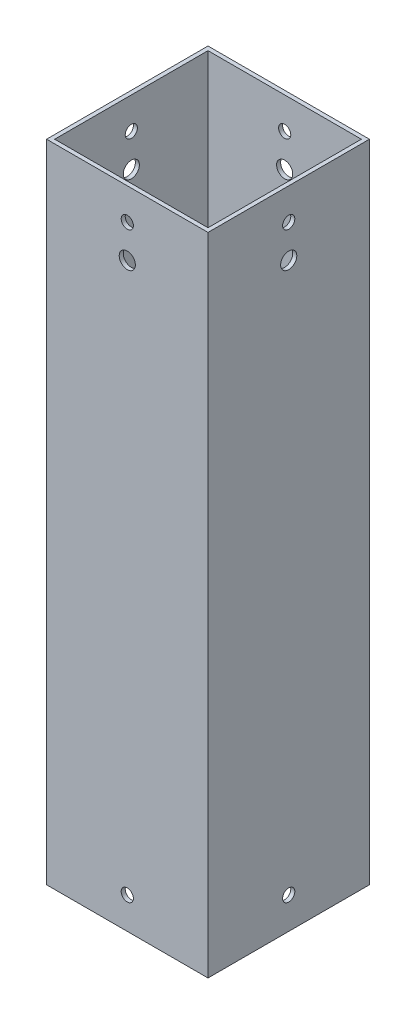
SolidWorks part; units mm, degrees
material "6061 Alloy"
ref_plane "Front Plane" through (0, 0, 0) normal (0, 0, 1) x (1, 0, 0)
ref_plane "Top Plane" through (0, 0, 0) normal (0, 1, 0) x (1, 0, 0)
ref_plane "Right Plane" through (0, 0, 0) normal (1, 0, 0) x (0, 0, -1)
sketch "Sketch1" plane through (0, 0, 0) normal (0, 1, 0) x (1, 0, 0)
  line L1 (-30.1625, 30.1625) -> (30.1625, 30.1625)
  line L2 (-30.1625, 30.1625) -> (-30.1625, -30.1625)
  line L3 (-30.1625, -30.1625) -> (30.1625, -30.1625)
  line L4 (30.1625, 30.1625) -> (30.1625, -30.1625)
  line L5 (-31.75, 31.75) -> (31.75, 31.75)
  line L6 (-31.75, 31.75) -> (-31.75, -31.75)
  line L7 (-31.75, -31.75) -> (31.75, -31.75)
  line L8 (31.75, 31.75) -> (31.75, -31.75)
  point P2 (-31.75, 0)
  point P11 (-30.1625, 0)
  point P12 (0, 30.1625)
  point P13 (0, 31.75)
  dimension "D1" = 60.325
  dimension "1.95" = 60.325
  dimension "2.05" = 63.5
  dimension "D2" = 63.5
extrude "Boss-Extrude1" add sketch "Sketch1" along normal blind 254
ref_plane "Plane1" through (0, 152.4, 0) normal (0, 1, 0) x (1, 0, 0)
sketch "Sketch3" plane through (0, 152.4, 0) normal (0, 1, 0) x (1, 0, 0)
  line L1 (-30.1625, 30.1625) -> (30.1625, 30.1625)
  line L2 (-30.1625, 30.1625) -> (-30.1625, -30.1625)
  line L3 (-30.1625, -30.1625) -> (30.1625, -30.1625)
  line L4 (30.1625, 30.1625) -> (30.1625, -30.1625)
extrude "Boss-Extrude3" add sketch "Sketch3" against normal blind 2.54
sketch "Sketch4" plane through (-30.1625, 0, 0) normal (1, 0, 0) x (0, 0, -1)
  line L0 (-31.75, 254) -> (31.75, 254) construction
  line L1 (31.75, 254) -> (31.75, 0) construction
  circle A0 centre (0, 241.5876) radius 2.4
  dimension "D1" = 4.8
  dimension "D2" = 12.4124
  dimension "D3" = 31.75
extrude "Cut-Extrude1" cut sketch "Sketch4" along normal through all both and the other way through all
sketch "Sketch5" plane through (0, 0, -31.75) normal (0, 0, -1) x (-1, 0, 0)
  line L0 (-31.75, 254) -> (31.75, 254) construction
  line L1 (31.75, 254) -> (31.75, 0) construction
  circle A0 centre (0, 241.5876) radius 2.4
  dimension "D1" = 4.8
  dimension "D2" = 12.4124
  dimension "D3" = 31.75
extrude "Cut-Extrude2" cut sketch "Sketch5" against normal through all
sketch "Sketch6" plane through (31.75, 0, 0) normal (1, 0, 0) x (0, 0, -1)
  line L0 (-31.75, 0) -> (31.75, 0) construction
  line L1 (31.75, 254) -> (31.75, 0) construction
  circle A0 centre (0, 12.4124) radius 2.4
  dimension "D1" = 12.4124
  dimension "D2" = 4.8
  dimension "D3" = 31.75
extrude "Cut-Extrude3" cut sketch "Sketch6" against normal through all both and the other way through all
sketch "Sketch7" plane through (0, 0, -31.75) normal (0, 0, -1) x (-1, 0, 0)
  line L0 (-31.75, 0) -> (31.75, 0) construction
  circle A0 centre (0, 12.4124) radius 2.4
  dimension "D1" = 4.8
  dimension "D2" = 12.4124
  dimension "D3" = 31.75
extrude "Cut-Extrude4" cut sketch "Sketch7" against normal through all both
sketch "Sketch8" plane through (0, 0, -31.75) normal (0, 0, -1) x (-1, 0, 0)
  line L0 (-31.75, 254) -> (31.75, 254) construction
  line L1 (-31.75, 254) -> (-31.75, 0) construction
  circle A0 centre (0, 228.6) radius 3.175
  dimension "D1" = 6.35
  dimension "D2" = 25.4
  dimension "D3" = 31.75
extrude "Cut-Extrude5" cut sketch "Sketch8" against normal through all both and the other way through all
sketch "Sketch9" plane through (31.75, 0, 0) normal (1, 0, 0) x (0, 0, -1)
  line L0 (-31.75, 254) -> (31.75, 254) construction
  line L1 (-31.75, 254) -> (-31.75, 0) construction
  circle A0 centre (0, 228.6) radius 3.175
  dimension "D1" = 6.35
  dimension "D2" = 25.4
  dimension "D3" = 31.75
extrude "Cut-Extrude6" cut sketch "Sketch9" against normal through all both
equation "\"1.95@Sketch1\"=2.5-(1/8)"
equation "\"D1@Sketch1\"=\"1.95@Sketch1\""
